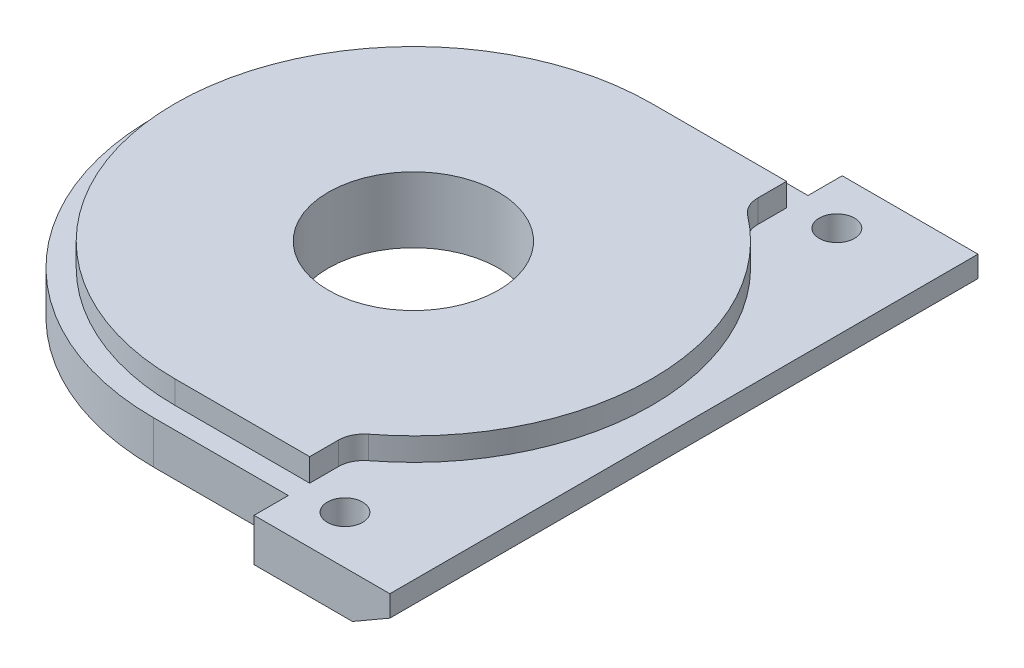
SolidWorks part; units mm, degrees
material "6061-T6 (SS)"
ref_plane "Front Plane" through (0, 0, 0) normal (0, 0, 1) x (1, 0, 0)
ref_plane "Top Plane" through (0, 0, 0) normal (0, 1, 0) x (1, 0, 0)
ref_plane "Right Plane" through (0, 0, 0) normal (1, 0, 0) x (0, 0, -1)
sketch "Sketch1" plane through (0, 0, 0) normal (0, 1, 0) x (1, 0, 0)
  line L0 (-13.2912, 20.8898) -> (-0.69, 20.8898)
  line L2 (-0.69, 24.0921) -> (-0.69, 20.8898)
  line L4 (12.01, 24.0921) -> (12.01, -26.9079)
  line L5 (-13.2912, -23.7056) -> (-0.69, -23.7056)
  line L6 (-0.69, -23.7056) -> (-0.69, -26.9079)
  line L13 (-0.69, -28.9079) -> (-0.69, -26.9079)
  line L15 (12.01, -28.9079) -> (12.01, -26.9079)
  line L16 (12.01, -28.9079) -> (-0.69, -28.9079)
  line L18 (12.01, 26.0921) -> (12.01, 24.0921)
  line L20 (-0.69, 26.0921) -> (-0.69, 24.0921)
  line L21 (-0.69, 26.0921) -> (12.01, 26.0921)
  arc A0 (-13.2912, 20.8898) -> (-13.2912, -23.7056) centre (-13.2912, -1.4079) ccw
extrude "Boss-Extrude1" add sketch "Sketch1" along normal blind 4
sketch "Sketch2" plane through (0, 4, 0) normal (0, 1, 0) x (1, 0, 0)
  line L0 (-0.69, 20.8898) -> (-0.69, 16.9877)
  line L1 (-0.69, -23.7056) -> (-0.69, -19.8035)
  line L2 (-0.69, -23.7056) -> (-13.2912, -23.7056)
  line L3 (-0.69, 20.8898) -> (-13.2912, 20.8898)
  arc A0 (-0.69, -19.8035) -> (-0.69, 16.9877) centre (-13.2912, -1.4079) ccw
  arc A1 (-13.2912, 20.8898) -> (-13.2912, -23.7056) centre (-13.2912, -1.4079) ccw
extrude "Boss-Extrude2" add sketch "Sketch2" along normal blind 2.25
sketch "Sketch3" plane through (0, 0, 0) normal (0, -1, 0) x (1, 0, 0)
  circle A0 centre (-13.2912, 1.4079) radius 7.95
  dimension "D1" = 15.9
extrude "Cut-Extrude1" cut sketch "Sketch3" against normal blind 9.25
sketch "Sketch4" plane through (0, 0, 0) normal (0, -1, 0) x (1, 0, 0)
  line L0 (-0.69, -26.0921) -> (3.31, -26.0921) construction
  line L1 (12.01, -26.0921) -> (-0.69, -26.0921) construction
  line L3 (3.31, -26.0921) -> (3.31, -21.5921) construction
  line L4 (-0.69, 28.9079) -> (3.31, 28.9079) construction
  line L5 (3.31, 28.9079) -> (3.31, 24.4079) construction
  circle A2 centre (3.31, -21.5921) radius 1.65
  circle A3 centre (3.31, 24.4079) radius 1.65
extrude "Cut-Extrude2" cut sketch "Sketch4" against normal blind 9.25
sketch "Sketch5" plane through (0, 0, 0) normal (0, -1, 0) x (1, 0, 0)
  line L9 (-20.9172, 10.6082) -> (-24.2357, 16.3644)
  line L12 (-17.4459, 12.6124) -> (-20.7716, 18.3644)
  line L14 (-1.5104, 3.4121) -> (5.1338, 3.4079)
  line L17 (-1.5104, -0.5963) -> (5.1338, -0.5921)
  line L19 (-17.4459, -9.7966) -> (-20.7716, -15.5486)
  line L22 (-20.9172, -7.7924) -> (-24.2357, -13.5486)
  circle A2 centre (-13.2912, 1.4079) radius 11.95
  arc A3 (-1.5104, 3.4121) -> (-17.4459, 12.6124) centre (-13.2912, 1.4079) ccw
  circle A4 centre (-13.2912, 1.4079) radius 18.45
  circle A5 centre (-13.2912, 1.4079) radius 18.45
  circle A6 centre (-13.2912, 1.4079) radius 18.45
  circle A7 centre (-13.2912, 1.4079) radius 18.45
  arc A8 (-20.9172, 10.6082) -> (-20.9172, -7.7924) centre (-13.2912, 1.4079) ccw
  arc A9 (-17.4459, -9.7966) -> (-1.5104, -0.5963) centre (-13.2912, 1.4079) ccw
  point P14 (-13.2912, 1.4079)
  dimension "D1" = 4
  dimension "D2" = 10.5
  dimension "D3" = 3
extrude "Cut-Extrude3" cut sketch "Sketch5" against normal blind 3 contours A8 L9 A4 L22 | L14 A4 L12 A3 | A9 L19 A4 L17 region at (-26.6764, 0, 1.4079) region at (-6.5986, 0, 12.9998) region at (-6.5986, 0, -10.184)
fillet "Fillet1" radius 2.3813 12 edges at (5.0501, 1.5, 3.4079) (-1.5104, 1.5, 3.4121) (5.0501, 1.5, -0.5922) (-24.1939, 1.5, 16.2919) (-20.7297, 1.5, 18.2919) (-1.5104, 1.5, -0.5963) (-20.7297, 1.5, -15.4761) (-20.9172, 1.5, 10.6082) (-20.9172, 1.5, -7.7924) (-24.1939, 1.5, -13.4761) (-17.4459, 1.5, -9.7966) (-17.4459, 1.5, 12.6124)
chamfer "Chamfer1" distance 3.5 angle 30 1 edges at (12.01, 0, 1.4079) first distance on face at (-7.8297, 0, -8.0516)
sketch "Sketch6" plane through (0, 0, 0) normal (0, -1, 0) x (1, 0, 0)
  line L2 (-0.69, -22.8898) -> (-13.2912, -22.8898)
  line L3 (-13.2912, 25.7056) -> (-0.69, 25.7056)
  line L4 (-0.69, -20.8898) -> (-13.2912, -20.8898)
  line L5 (-13.2912, 23.7056) -> (-0.69, 23.7056)
  line L6 (-0.69, -20.8898) -> (-13.2912, -20.8898)
  line L7 (-13.2912, 23.7056) -> (-0.69, 23.7056)
  line L8 (-0.69, 25.7056) -> (-0.69, 23.7056)
  line L9 (-0.69, -20.8898) -> (-0.69, -22.8898)
  arc A1 (-13.2912, 25.7056) -> (-13.2912, -22.8898) centre (-13.2912, 1.4079) ccw
  arc A2 (-13.2912, 23.7056) -> (-13.2912, -20.8898) centre (-13.2912, 1.4079) ccw
  arc A3 (-13.2912, 23.7056) -> (-13.2912, -20.8898) centre (-13.2912, 1.4079) ccw
  dimension "D1" = 0
  dimension "D2" = 2
extrude "Boss-Extrude3" add sketch "Sketch6" against normal blind 4
ref_axis "Axis2" through (-13.2912, 6.25, 1.4079) along (0, -1, 0)
sketch "Sketch7" plane through (0, 6.25, 0) normal (0, 1, 0) x (1, 0, 0)
  line L1 (-41.0707, -28.482) -> (15.4918, -28.482)
  line L2 (-41.0707, -28.482) -> (-41.0707, 23.4819)
  line L3 (-41.0707, 23.4819) -> (15.4918, 23.4819)
  line L4 (15.4918, -28.482) -> (15.4918, 23.4819)
extrude "Cut-Extrude4" cut sketch "Sketch7" against normal blind 0.1
fillet "Fillet3" radius 2.38 2 edges at (-0.69, 5.075, -16.9877) (-0.69, 5.075, 19.8035)
